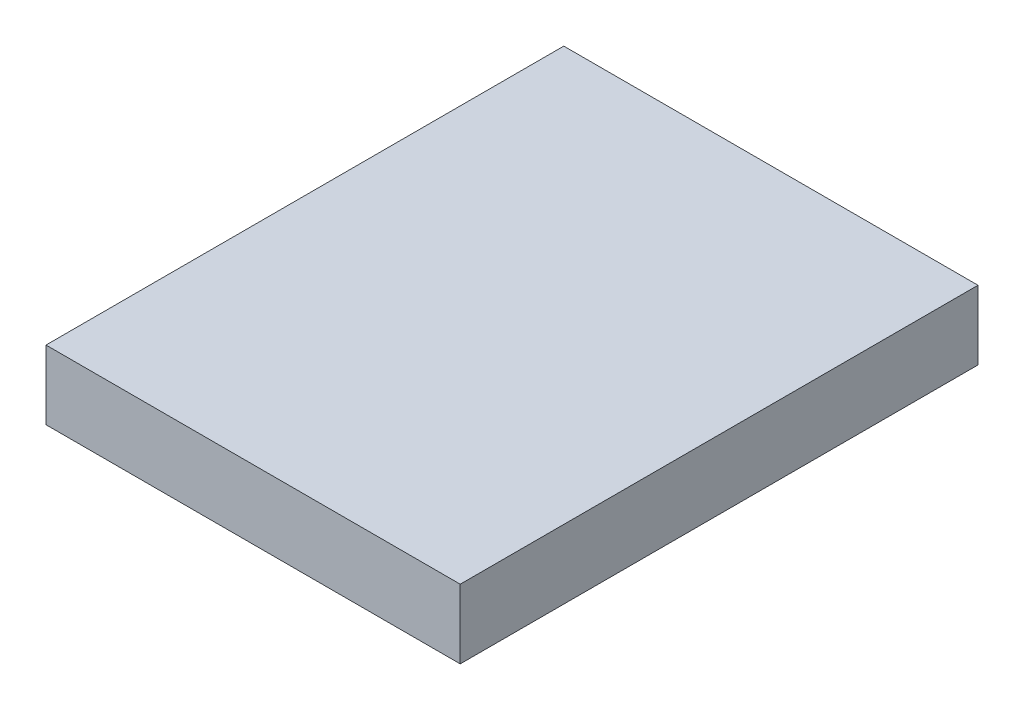
SolidWorks part; units mm, degrees
ref_plane "Front Plane" through (0, 0, 0) normal (0, 0, 1) x (1, 0, 0)
ref_plane "Top Plane" through (0, 0, 0) normal (0, 1, 0) x (1, 0, 0)
ref_plane "Right Plane" through (0, 0, 0) normal (1, 0, 0) x (0, 0, -1)
sketch "Sketch1" plane through (0, 0, 0) normal (0, 1, 0) x (1, 0, 0)
  line L1 (0, 0) -> (229, 0)
  line L2 (0, 0) -> (0, -12.7)
  line L3 (0, -12.7) -> (229, -12.7)
  line L4 (229, 0) -> (229, -12.7)
  dimension "D1" = 229
  dimension "D2" = 12.7
extrude "Boss-Extrude1" add sketch "Sketch1" against normal blind 1
sketch "Sketch2" [suppressed] plane through (0, 0, 0) normal (0, 1, 0) x (1, 0, 0)
  line L0 (229, -12.7) -> (229, 0) construction
  line L1 (0, -12.7) -> (229, -12.7)
  line L2 (0, -12.7) -> (0, -6)
  line L3 (0, -6) -> (229, -6)
  line L4 (229, -12.7) -> (229, -6)
  line L5 (229, 0) -> (0, 0) construction
  dimension "D1" = 6
extrude "Cut-Extrude1" [suppressed] cut sketch "Sketch2" against normal through all
sketch "Sketch3" [suppressed] plane through (0, 0, 0) normal (0, 1, 0) x (1, 0, 0)
  line L0 (229, -12.7) -> (229, 0) construction
  line L1 (0, -12.7) -> (229, -12.7)
  line L2 (0, -12.7) -> (0, -8.5)
  line L3 (0, -8.5) -> (229, -8.5)
  line L4 (229, -12.7) -> (229, -8.5)
  line L5 (229, 0) -> (0, 0) construction
  dimension "D1" = 8.5
extrude "Cut-Extrude2" [suppressed] cut sketch "Sketch3" against normal through all
sketch "Sketch4" plane through (0, 0, 0) normal (0, 1, 0) x (1, 0, 0)
  line L0 (229, 0) -> (0, 0) construction
  line L1 (229, -12.7) -> (6, -12.7)
  line L2 (229, -12.7) -> (229, 0)
  line L3 (229, 0) -> (6, 0)
  line L4 (6, -12.7) -> (6, 0)
  line L5 (0, 0) -> (0, -12.7) construction
  line L7 (6, -12.7) -> (0, -12.7)
  line L8 (6, -12.7) -> (6, -7.5)
  line L9 (6, -7.5) -> (0, -7.5)
  line L10 (0, -12.7) -> (0, -7.5)
  line M4 (0, -12.7) -> (229, -12.7)
  line M5 (229, -12.7) -> (229, 0)
  line M6 (229, 0) -> (0, 0)
  dimension "D1" = 6
  dimension "D2" = 7.5
extrude "Cut-Extrude3" cut sketch "Sketch4" against normal through all contours L4 M4 M5 M6 | L7 L10 L9 L8 region at (117.5, 0, 6.35)
sketch "Sketch5" [suppressed] plane through (0, 0, 0) normal (0, 1, 0) x (1, 0, 0)
  line L0 (228.6, 0) -> (0, 0) construction
  line L1 (228.6, -12.7) -> (9.3, -12.7)
  line L2 (228.6, -12.7) -> (228.6, 0)
  line L3 (228.6, 0) -> (9.3, 0)
  line L4 (9.3, -12.7) -> (9.3, 0)
  line L6 (0, -12.7) -> (9.3, -12.7)
  line L7 (0, -12.7) -> (0, -9.3)
  line L8 (0, -9.3) -> (9.3, -9.3)
  line L9 (9.3, -12.7) -> (9.3, -9.3)
  dimension "D1" = 9.3
  dimension "D2" = 9.3
extrude "Cut-Extrude4" [suppressed] cut sketch "Sketch5" against normal through all
sketch "Sketch6" [suppressed] plane through (0, -0.8, 0) normal (0, -1, 0) x (1, 0, 0)
  line L0 (0, 12.7) -> (228.6, 12.7) construction
  line L1 (228.6, 0) -> (9.3, 0)
  line L2 (228.6, 0) -> (228.6, 12.7)
  line L3 (228.6, 12.7) -> (9.3, 12.7)
  line L4 (9.3, 0) -> (9.3, 12.7)
  line L5 (228.6, 0) -> (0, 0) construction
  line L6 (0, 12.7) -> (9.3, 12.7)
  line L7 (0, 12.7) -> (0, 6.2)
  line L8 (0, 6.2) -> (9.3, 6.2)
  line L9 (9.3, 12.7) -> (9.3, 6.2)
  dimension "D1" = 9.3
  dimension "D2" = 6.2
extrude "Cut-Extrude5" [suppressed] cut sketch "Sketch6" against normal through all
sketch "Sketch7" [suppressed] plane through (0, -0.8, 0) normal (0, -1, 0) x (1, 0, 0)
  line L0 (0, 12.7) -> (228.6, 12.7) construction
  line L1 (228.6, 0) -> (8.5, 0)
  line L2 (228.6, 0) -> (228.6, 12.7)
  line L3 (228.6, 12.7) -> (8.5, 12.7)
  line L4 (8.5, 0) -> (8.5, 12.7)
  line L6 (0, 12.7) -> (8.5, 12.7)
  line L7 (0, 12.7) -> (0, 6.2)
  line L8 (0, 6.2) -> (8.5, 6.2)
  line L9 (8.5, 12.7) -> (8.5, 6.2)
  line L10 (228.6, 0) -> (0, 0) construction
  dimension "D1" = 8.5
  dimension "D2" = 6.2
extrude "Cut-Extrude6" [suppressed] cut sketch "Sketch7" against normal through all
